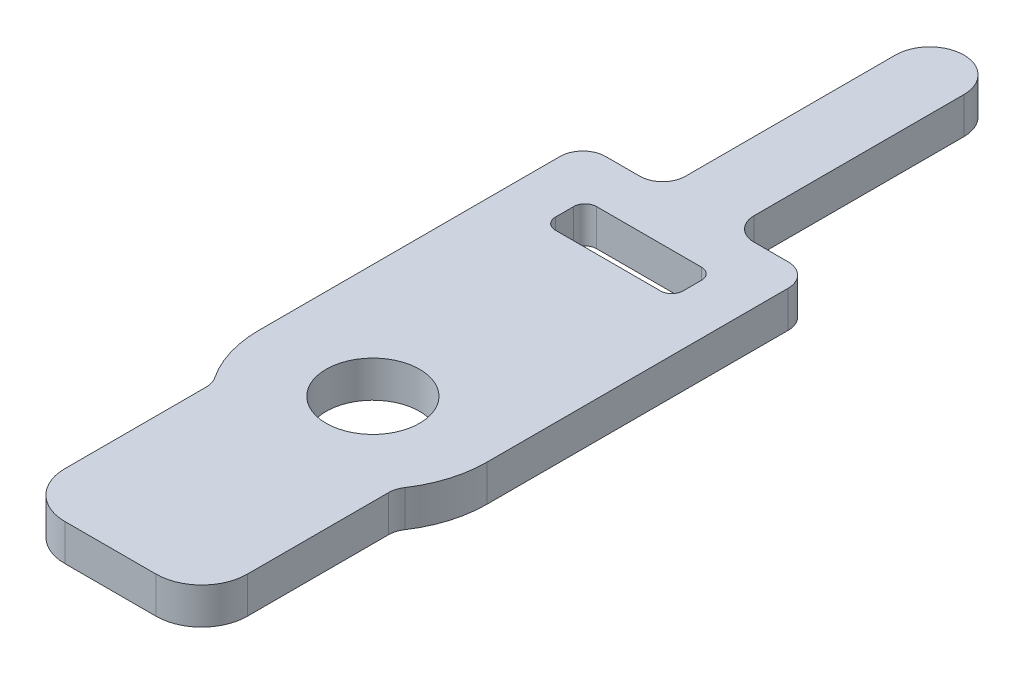
SolidWorks part; units mm, degrees
ref_plane "前视基准面" through (0, 0, 0) normal (0, 0, 1) x (1, 0, 0)
ref_plane "上视基准面" through (0, 0, 0) normal (0, 1, 0) x (1, 0, 0)
ref_plane "右视基准面" through (0, 0, 0) normal (1, 0, 0) x (0, 0, -1)
sketch "草图1" plane through (0, 0, 0) normal (0, 1, 0) x (1, 0, 0)
  line L0 (0, 0) -> (0, 40.3281) construction
  line L1 (2.5, 0) -> (2.5, 20.4566) construction
  line L2 (0, 37.4) -> (1.5, 37.4)
  line L4 (0, 0) -> (4, 0)
  line L5 (5, 25.7) -> (5, 11.5)
  line L6 (4, 0) -> (4, 8.5)
  line L7 (0, 37.4) -> (0, 23.6)
  line L8 (0, 9.45) -> (0, 0)
  line L9 (5, 25.7) -> (1.5, 25.7)
  line L10 (1.5, 25.7) -> (1.5, 37.4)
  line L11 (2.8, 21.8) -> (0, 21.8)
  line L13 (2.8, 23.6) -> (0, 23.6)
  line L14 (0, 21.8) -> (0, 13.55)
  line L15 (2.8, 21.8) -> (2.8, 23.6)
  line L16 (2.5, 22.7) -> (6.9708, 22.7) construction
  arc A0 (0, 9.45) -> (0, 13.55) centre (0, 11.5) ccw
  arc A1 (4, 8.5) -> (5, 11.5) centre (0, 11.5) ccw
  point P14 (2.8, 22.7)
  dimension "D1" = 4.1
  dimension "D9" = 1.8
  dimension "D2" = 5
  dimension "D3" = 2.5
  dimension "D4" = 4
  dimension "D5" = 11.5
  dimension "D6" = 14.2
  dimension "D7" = 37.4
  dimension "D8" = 1.5
  dimension "D10" = 0.3
  dimension "D11" = 11.2
extrude "凸台-拉伸1" add sketch "草图1" along normal blind 1.6
fillet "圆角1" radius 2 1 edges at (4, 0.8, 0)
fillet "圆角2" radius 1.5 1 edges at (1.5, 0.8, -37.4)
fillet "圆角3" radius 1 3 edges at (4, 0.8, -8.5) (5, 0.8, -25.7) (1.5, 0.8, -25.7)
fillet "圆角4" radius 0.5 2 edges at (2.8, 0.8, -23.6) (2.8, 0.8, -21.8)
mirror "镜向1" about plane through (0, 1.6, -37.4) normal (1, 0, 0) of bodies 106
sketch "草图2" plane through (0, 0, 0) normal (0, -1, 0) x (1, 0, 0)
